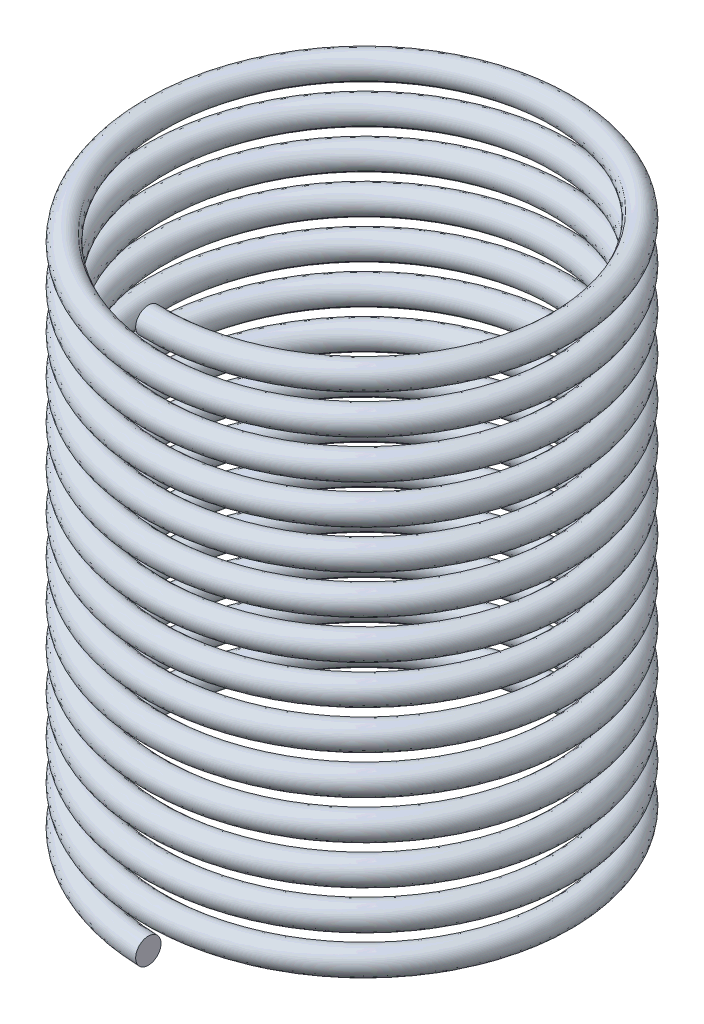
SolidWorks part; units mm, degrees
ref_plane "Front Plane" through (0, 0, 0) normal (0, 0, 1) x (1, 0, 0)
ref_plane "Top Plane" through (0, 0, 0) normal (0, 1, 0) x (1, 0, 0)
ref_plane "Right Plane" through (0, 0, 0) normal (1, 0, 0) x (0, 0, -1)
sketch "Sketch1" plane through (0, 0, 0) normal (0, 1, 0) x (1, 0, 0)
  circle A0 centre (0, 0) radius 10.4375
  dimension "D1" = 20.875
curve "Helix/Spiral1" pitch 2 height 28 radius 10.4375 left hand yes centre (0, 0, 0) axis (0, 1, 0) start towards (0, 0, 1)
sketch "Sketch2" plane through (0, 0, 0) normal (1, 0, 0) x (0, 0, -1)
  circle A0 centre (-10.4375, 0) radius 0.65
  spline S0 degree 3 poles (-10.4375, 0) (-10.4375, 0.0414) (-9.894, 0.1251) (-7.5726, 0.25) (-4.0982, 0.375) (0, 0.5) (4.0982, 0.625) (7.5726, 0.75) (9.894, 0.875) (10.7092, 1) (9.894, 1.125) (7.5726, 1.25) (2.9401, 1.4167) (-2.9401, 1.5833) (-7.5726, 1.75) (-9.894, 1.875) (-10.7092, 2) (-9.894, 2.125) (-7.5726, 2.25) (-2.9401, 2.4167) (2.9401, 2.5833) (7.5726, 2.75) (9.894, 2.875) (10.7092, 3) (9.894, 3.125) (7.5726, 3.25) (2.9401, 3.4167) (-2.9401, 3.5833) (-7.5726, 3.75) (-9.894, 3.875) (-10.7092, 4) (-9.894, 4.125) (-7.5726, 4.25) (-2.9401, 4.4167) (2.9401, 4.5833) (7.5726, 4.75) (9.894, 4.875) (10.7092, 5) (9.894, 5.125) (7.5726, 5.25) (2.9401, 5.4167) (-2.9401, 5.5833) (-7.5726, 5.75) (-9.894, 5.875) (-10.7092, 6) (-9.894, 6.125) (-7.5726, 6.25) (-2.9401, 6.4167) (2.9401, 6.5833) (7.5726, 6.75) (9.894, 6.875) (10.7092, 7) (9.894, 7.125) (7.5726, 7.25) (2.9401, 7.4167) (-2.9401, 7.5833) (-7.5726, 7.75) (-9.894, 7.875) (-10.7092, 8) (-9.894, 8.125) (-7.5726, 8.25) (-2.9401, 8.4167) (2.9401, 8.5833) (7.5726, 8.75) (9.894, 8.875) (10.7092, 9) (9.894, 9.125) (7.5726, 9.25) (2.9401, 9.4167) (-2.9401, 9.5833) (-7.5726, 9.75) (-9.894, 9.875) (-10.7092, 10) (-9.894, 10.125) (-7.5726, 10.25) (-2.9401, 10.4167) (2.9401, 10.5833) (7.5726, 10.75) (9.894, 10.875) (10.7092, 11) (9.894, 11.125) (7.5726, 11.25) (2.9401, 11.4167) (-2.9401, 11.5833) (-7.5726, 11.75) (-9.894, 11.875) (-10.7092, 12) (-9.894, 12.125) (-7.5726, 12.25) (-2.9401, 12.4167) (2.9401, 12.5833) (7.5726, 12.75) (9.894, 12.875) (10.7092, 13) (9.894, 13.125) (7.5726, 13.25) (2.9401, 13.4167) (-2.9401, 13.5833) (-7.5726, 13.75) (-9.894, 13.875) (-10.7092, 14) (-9.894, 14.125) (-7.5726, 14.25) (-2.9401, 14.4167) (2.9401, 14.5833) (7.5726, 14.75) (9.894, 14.875) (10.7092, 15) (9.894, 15.125) (7.5726, 15.25) (2.9401, 15.4167) (-2.9401, 15.5833) (-7.5726, 15.75) (-9.894, 15.875) (-10.7092, 16) (-9.894, 16.125) (-7.5726, 16.25) (-2.9401, 16.4167) (2.9401, 16.5833) (7.5726, 16.75) (9.894, 16.875) (10.7092, 17) (9.894, 17.125) (7.5726, 17.25) (2.9401, 17.4167) (-2.9401, 17.5833) (-7.5726, 17.75) (-9.894, 17.875) (-10.7092, 18) (-9.894, 18.125) (-7.5726, 18.25) (-2.9401, 18.4167) (2.9401, 18.5833) (7.5726, 18.75) (9.894, 18.875) (10.7092, 19) (9.894, 19.125) (7.5726, 19.25) (2.9401, 19.4167) (-2.9401, 19.5833) (-7.5726, 19.75) (-9.894, 19.875) (-10.7092, 20) (-9.894, 20.125) (-7.5726, 20.25) (-2.9401, 20.4167) (2.9401, 20.5833) (7.5726, 20.75) (9.894, 20.875) (10.7092, 21) (9.894, 21.125) (7.5726, 21.25) (2.9401, 21.4167) (-2.9401, 21.5833) (-7.5726, 21.75) (-9.894, 21.875) (-10.7092, 22) (-9.894, 22.125) (-7.5726, 22.25) (-2.9401, 22.4167) (2.9401, 22.5833) (7.5726, 22.75) (9.894, 22.875) (10.7092, 23) (9.894, 23.125) (7.5726, 23.25) (2.9401, 23.4167) (-2.9401, 23.5833) (-7.5726, 23.75) (-9.894, 23.875) (-10.7092, 24) (-9.894, 24.125) (-7.5726, 24.25) (-2.9401, 24.4167) (2.9401, 24.5833) (7.5726, 24.75) (9.894, 24.875) (10.7092, 25) (9.894, 25.125) (7.5726, 25.25) (2.9401, 25.4167) (-2.9401, 25.5833) (-7.5726, 25.75) (-9.894, 25.875) (-10.7092, 26) (-9.894, 26.125) (-7.5726, 26.25) (-2.9401, 26.4167) (2.9401, 26.5833) (7.5726, 26.75) (9.894, 26.875) (10.7092, 27) (9.894, 27.125) (7.5726, 27.25) (4.0982, 27.375) (0, 27.5) (-4.0982, 27.625) (-7.5726, 27.75) (-9.894, 27.8749) (-10.4375, 27.9586) (-10.4375, 28) knots 0 0 0 0 0.004464 0.008929 0.013393 0.017857 0.022321 0.026786 0.03125 0.035714 0.040179 0.044643 0.049107 0.058036 0.0625 0.066964 0.071429 0.075893 0.080357 0.084821 0.09375 0.098214 0.102679 0.107143 0.111607 0.116071 0.120536 0.129464 0.133929 0.138393 0.142857 0.147321 0.151786 0.15625 0.165179 0.169643 0.174107 0.178571 0.183036 0.1875 0.191964 0.200893 0.205357 0.209821 0.214286 0.21875 0.223214 0.227679 0.236607 0.241071 0.245536 0.25 0.254464 0.258929 0.263393 0.272321 0.276786 0.28125 0.285714 0.290179 0.294643 0.299107 0.308036 0.3125 0.316964 0.321429 0.325893 0.330357 0.334821 0.34375 0.348214 0.352679 0.357143 0.361607 0.366071 0.370536 0.379464 0.383929 0.388393 0.392857 0.397321 0.401786 0.40625 0.415179 0.419643 0.424107 0.428571 0.433036 0.4375 0.441964 0.450893 0.455357 0.459821 0.464286 0.46875 0.473214 0.477679 0.486607 0.491071 0.495536 0.5 0.504464 0.508929 0.513393 0.522321 0.526786 0.53125 0.535714 0.540179 0.544643 0.549107 0.558036 0.5625 0.566964 0.571429 0.575893 0.580357 0.584821 0.59375 0.598214 0.602679 0.607143 0.611607 0.616071 0.620536 0.629464 0.633929 0.638393 0.642857 0.647321 0.651786 0.65625 0.665179 0.669643 0.674107 0.678571 0.683036 0.6875 0.691964 0.700893 0.705357 0.709821 0.714286 0.71875 0.723214 0.727679 0.736607 0.741071 0.745536 0.75 0.754464 0.758929 0.763393 0.772321 0.776786 0.78125 0.785714 0.790179 0.794643 0.799107 0.808036 0.8125 0.816964 0.821429 0.825893 0.830357 0.834821 0.84375 0.848214 0.852679 0.857143 0.861607 0.866071 0.870536 0.879464 0.883929 0.888393 0.892857 0.897321 0.901786 0.90625 0.915179 0.919643 0.924107 0.928571 0.933036 0.9375 0.941964 0.950893 0.955357 0.959821 0.964286 0.96875 0.973214 0.977679 0.982143 0.986607 0.991071 0.995536 1 1 1 1 construction
  dimension "D1" = 1.3
sweep "Sweep1" add profiles "Sketch2" path "Helix/Spiral1"
ref_plane "Bottom Face" through (0, 0, 0) normal (0, 1, 0) x (1, 0, 0)
ref_plane "Top Face" through (0, 28.65, 0) normal (0, 1, 0) x (1, 0, 0)
ref_axis "Axis1" through (0, -2.83, 0) along (0, 1, 0)
equation "\"innerDiameter\"= 5in / 8"
equation "\"springLength\"= 28mm"
equation "\"D1@Sketch1\"=\"innerDiameter\" + 5"
